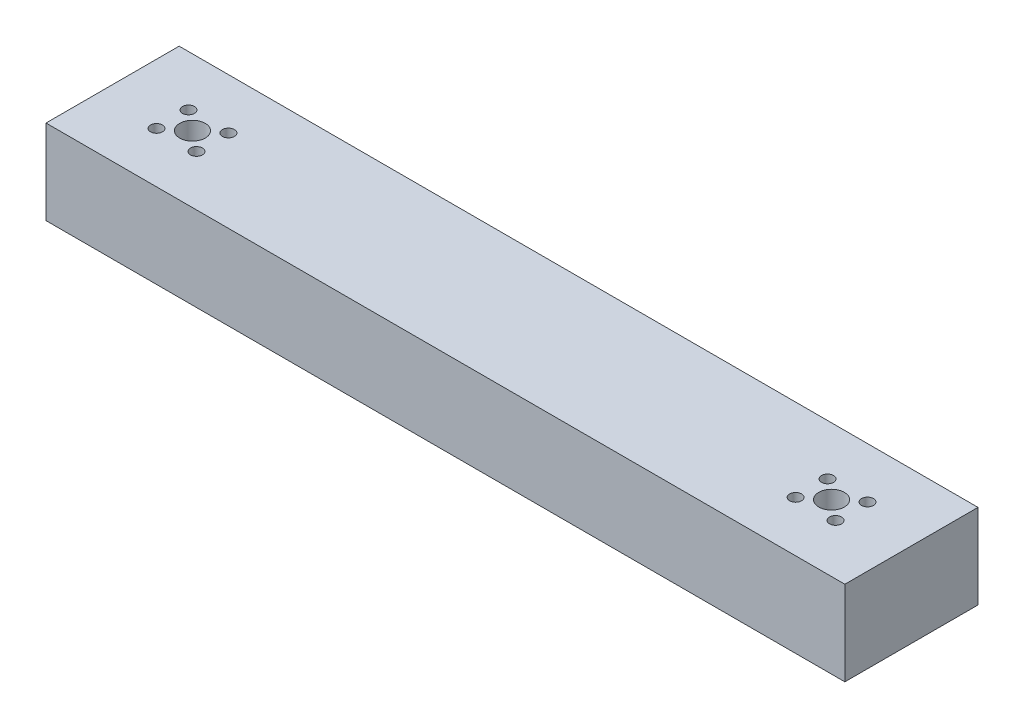
SolidWorks part; units mm, degrees
ref_plane "Front Plane" through (0, 0, 0) normal (0, 0, 1) x (1, 0, 0)
ref_plane "Top Plane" through (0, 0, 0) normal (0, 1, 0) x (1, 0, 0)
ref_plane "Right Plane" through (0, 0, 0) normal (1, 0, 0) x (0, 0, -1)
sketch "Sketch2" plane through (0, 0, 0) normal (0, 1, 0) x (1, 0, 0)
  line L1 (0, 0) -> (300, 0)
  line L2 (0, 0) -> (0, 50)
  line L3 (0, 50) -> (300, 50)
  line L4 (300, 0) -> (300, 50)
  dimension "D1" = 300
  dimension "D2" = 50
extrude "Boss-Extrude1" add sketch "Sketch2" along normal blind 31.75
sketch "Sketch3" plane through (0, 31.75, 0) normal (0, 1, 0) x (1, 0, 0)
  line L0 (30, 25) -> (37.5, 25)
  line L2 (37.5, 25) -> (37.5, 31)
  line L3 (37.5, 25) -> (37.5, 19)
  line L4 (30, 25) -> (10, 25)
  line L5 (30, 25) -> (22.5, 25)
  line L6 (22.5, 25) -> (22.5, 31)
  line L7 (10, 25) -> (10, 10)
  line L8 (270, 25) -> (277.5, 25)
  line L10 (277.5, 25) -> (277.5, 31)
  line L11 (270, 25) -> (262.5, 25)
  line L12 (262.5, 25) -> (262.5, 31)
  line L13 (262.5, 25) -> (262.5, 19)
  line L14 (277.5, 25) -> (277.5, 19)
  line L16 (22.5, 25) -> (22.5, 19)
  circle A0 centre (30, 25) radius 4.8
  circle A1 centre (270, 25) radius 4.8
  circle A10 centre (30, 25) radius 12.7
  circle A11 centre (37.5, 31) radius 2.25
  circle A12 centre (37.5, 19) radius 2.25
  circle A13 centre (22.5, 31) radius 2.25
  circle A14 centre (22.5, 19) radius 2.25
  circle A15 centre (270, 25) radius 12.7
  circle A17 centre (262.5, 31) radius 2.25
  circle A18 centre (262.5, 19) radius 2.25
  circle A19 centre (277.5, 31) radius 2.25
  circle A20 centre (277.5, 19) radius 2.25
  dimension "D2" = 9.6
  dimension "D8" = 9.6
  dimension "D11" = 4.5
  dimension "D12" = 6
  dimension "D13" = 7.5
  dimension "D14" = 4.5
  dimension "D15" = 4.5
  dimension "D16" = 4.5
  dimension "D17" = 4.5
  dimension "D18" = 4.5
  dimension "D3" = 25.4
  dimension "D19" = 4.5
  dimension "D20" = 4.5
  dimension "D7" = 25.4
  dimension "D4" = 7.5
  dimension "D5" = 20
  dimension "D6" = 6
  dimension "D9" = 7.5
  dimension "D10" = 7.5
extrude "Cut-Extrude1" cut sketch "Sketch3" against normal blind 31.75 contours A14 | L4 A0 | A0 L4 | A20 | A1 | A1 region at (30, 31.75, -27.0372) region at (30, 31.75, -22.9628) region at (24.046, 31.75, -20.546) region at (270, 31.75, -27.0372) region at (270, 31.75, -22.9628) region at (279.046, 31.75, -20.546)
extrude "Cut-Extrude2" cut sketch "Sketch3<3>" against normal blind 31.75 contours A13 | A11 | A12 | A19 | A17 | A18 region at (35.954, 31.75, -32.546) region at (39.046, 31.75, -20.546) region at (20.954, 31.75, -32.546) region at (275.954, 31.75, -32.546) region at (264.046, 31.75, -20.546) region at (260.954, 31.75, -32.546)
sketch "Sketch3<3>" plane through (0, 31.75, 0) normal (0, 1, 0) x (1, 0, 0) same geometry as "Sketch3"
